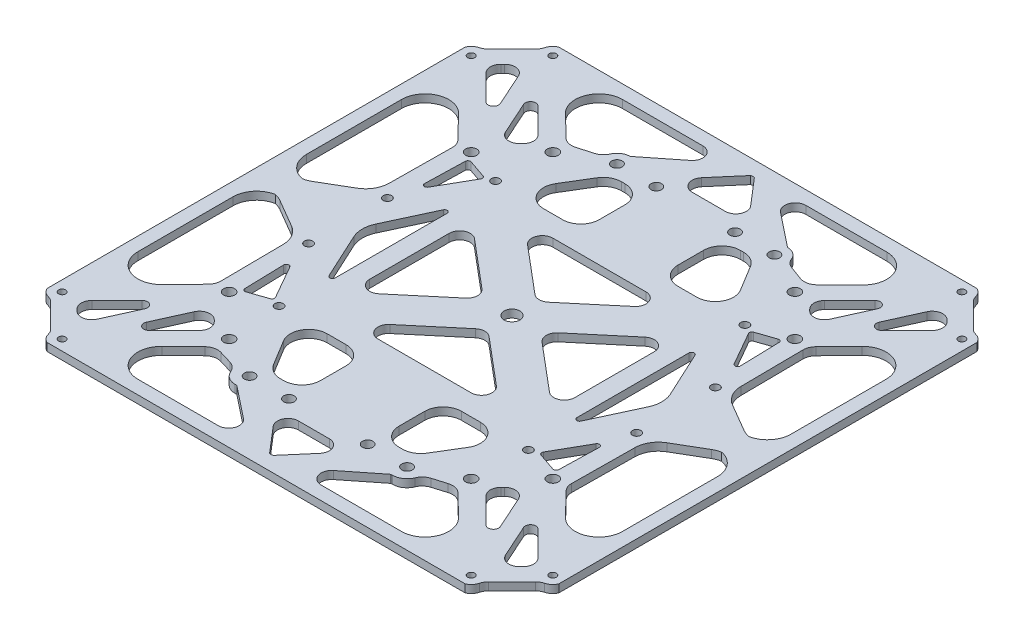
SolidWorks part; units mm, degrees
material "Thornel Mat VMA"
ref_plane "Front Plane" through (0, 0, 0) normal (0, 0, 1) x (1, 0, 0)
ref_plane "Top Plane" through (0, 0, 0) normal (0, 1, 0) x (1, 0, 0)
ref_plane "Right Plane" through (0, 0, 0) normal (1, 0, 0) x (0, 0, -1)
sketch "Sketch2" plane through (0, 0, 0) normal (0, 1, 0) x (1, 0, 0)
  line L1 (-97.5, -97.5) -> (97.5, -97.5)
  line L2 (-97.5, -97.5) -> (-97.5, 97.5)
  line L3 (-97.5, 97.5) -> (97.5, 97.5)
  line L4 (97.5, -97.5) -> (97.5, 97.5)
  line L5 (-97.5, -97.5) -> (97.5, 97.5) construction
  line L6 (-97.5, 97.5) -> (97.5, -97.5) construction
  point P0 (0, 0)
  dimension "D1" = 195
  dimension "D2" = 195
extrude "Boss-Extrude1" add sketch "Sketch2" along normal blind 3
sketch "Sketch3" plane through (0, 3, 0) normal (0, 1, 0) x (1, 0, 0)
  circle A2 centre (47.5, 41.25) radius 1.6
  circle A3 centre (47.5, -41.25) radius 1.6
  circle A4 centre (-47.5, -41.25) radius 1.6
  circle A5 centre (-47.5, 41.25) radius 1.6
  dimension "D3" = 3.2
extrude "Cut-Extrude1" cut sketch "Sketch3" against normal through all both and the other way through all
sketch "Sketch4" plane through (0, 3, 0) normal (0, 1, 0) x (1, 0, 0)
  line L4 (97.5, 97.5) -> (-97.5, 97.5) construction
  circle A0 centre (46.1238, 61.6802) radius 2.11
  circle A3 centre (-61.6802, 46.1238) radius 2.11
  circle A5 centre (-77.9437, 93.5) radius 1.35
  circle A6 centre (-93.5, 77.9437) radius 1.35
  circle A7 centre (-46.1238, 61.6802) radius 2.11
  circle A8 centre (93.5, 77.9437) radius 1.35
  circle A9 centre (77.9437, 93.5) radius 1.35
  circle A10 centre (61.6802, 46.1238) radius 2.11
  circle A11 centre (61.6802, -46.1238) radius 2.11
  circle A12 centre (77.9437, -93.5) radius 1.35
  circle A13 centre (93.5, -77.9437) radius 1.35
  circle A14 centre (-46.1238, -61.6802) radius 2.11
  circle A15 centre (-93.5, -77.9437) radius 1.35
  circle A16 centre (-77.9437, -93.5) radius 1.35
  circle A17 centre (-61.6802, -46.1238) radius 2.11
  circle A18 centre (46.1238, -61.6802) radius 2.11
  dimension "D1" = 2.7
  dimension "D3" = 4.22
  dimension "D6" = 4
extrude "Cut-Extrude2" cut sketch "Sketch4" against normal through all both and the other way through all
sketch "Sketch5" plane through (0, 3, 0) normal (0, 1, 0) x (1, 0, 0)
  circle A1 centre (30, 70) radius 2
  circle A2 centre (15, 70) radius 2
  circle A3 centre (-15, 70) radius 2
  circle A4 centre (-30, 70) radius 2
  circle A5 centre (-30, -70) radius 2
  circle A6 centre (-15, -70) radius 2
  circle A7 centre (15, -70) radius 2
  circle A8 centre (30, -70) radius 2
  dimension "D3" = 4
  dimension "D4" = 4
  dimension "D1" = 4
  dimension "D2" = 4
  dimension "D5" = 4
  dimension "D6" = 4
  dimension "D7" = 4
  dimension "D8" = 4
extrude "Cut-Extrude3" cut sketch "Sketch5" against normal through all both and the other way through all
sketch "Sketch6" plane through (0, 3, 0) normal (0, 1, 0) x (1, 0, 0)
  circle A2 centre (-62.5, 15) radius 1.6
  circle A3 centre (-62.5, -15) radius 1.6
  circle A4 centre (62.5, -15) radius 1.6
  circle A5 centre (62.5, 15) radius 1.6
  dimension "D2" = 3.2
extrude "Cut-Extrude4" cut sketch "Sketch6" against normal through all both and the other way through all
sketch "Sketch7" plane through (0, 3, 0) normal (0, 1, 0) x (1, 0, 0)
  line L0 (-68.2257, 47.6002) -> (-92.338, 72.3986)
  line L1 (-92.3432, 83.4505) -> (-83.4505, 92.3432)
  line L2 (-72.3986, 92.338) -> (-48.2358, 68.8437)
  line L3 (-43.3841, 67.6187) -> (-37.7917, 69.2071)
  line L4 (-67.1, 15) -> (-66.8107, 44.0648)
  line L5 (-30, 75) -> (-15, 75)
  line L6 (-15, 75) -> (15, 75)
  line L7 (15, 75) -> (30, 75)
  line L8 (37.5401, 69.065) -> (42.7993, 67.1289)
  line L9 (48.04, 68.2636) -> (72.4199, 92.3408)
  line L10 (83.4505, 92.3432) -> (92.3432, 83.4505)
  line L11 (68.2257, 47.6002) -> (92.338, 72.3986)
  line L12 (66.8107, 44.0648) -> (67.1, 15)
  line L13 (-67.1, -15) -> (-67.0991, 15.0916)
  line L14 (66.8107, -44.0648) -> (67.1, -15)
  line L15 (68.2257, -47.6002) -> (92.338, -72.3986)
  line L16 (83.4505, -92.3432) -> (92.3432, -83.4505)
  line L17 (48.2358, -68.8437) -> (72.3986, -92.338)
  line L18 (38.2846, -69.1587) -> (43.3041, -67.6421)
  line L19 (15, -75.5) -> (30, -75.5)
  line L20 (-15, -75.5) -> (15, -75.5)
  line L21 (-30, -75.5) -> (-15, -75.5)
  line L22 (-67.1, -15) -> (-66.8107, -44.0648)
  line L23 (-43.3041, -67.6421) -> (-38.2846, -69.1587)
  line L24 (-72.3986, -92.338) -> (-48.2358, -68.8437)
  line L25 (-92.3432, -83.4505) -> (-83.4505, -92.3432)
  line L26 (-68.2257, -47.6002) -> (-92.338, -72.3986)
  line L27 (67.0991, -15.0916) -> (67.1, 15)
  line L29 (-123.1678, -119.5363) -> (123.1678, -119.5363)
  line L30 (-123.1678, -119.5363) -> (-123.1678, 119.5363)
  line L31 (-123.1678, 119.5363) -> (123.1678, 119.5363)
  line L32 (123.1678, -119.5363) -> (123.1678, 119.5363)
  line L33 (-123.1678, -119.5363) -> (123.1678, 119.5363) construction
  line L34 (-123.1678, 119.5363) -> (123.1678, -119.5363) construction
  arc A0 (68.2257, 47.6002) -> (66.8107, 44.0648) centre (71.8104, 44.1146) ccw
  arc A1 (42.7993, 67.1289) -> (48.04, 68.2636) centre (44.5266, 71.8211) ccw
  arc A2 (37.5401, 69.065) -> (34.6337, 71.8786) centre (39.2674, 73.7571) cw
  arc A3 (-37.7917, 69.2071) -> (-34.5789, 72.0084) centre (-39.1578, 74.0168) ccw
  arc A4 (-48.2358, 68.8437) -> (-43.3841, 67.6187) centre (-44.7502, 72.4285) ccw
  arc A5 (-66.8107, 44.0648) -> (-68.2257, 47.6002) centre (-71.8104, 44.1146) ccw
  arc A6 (-92.338, 72.3986) -> (-94.6272, 73.7422) centre (-95.9228, 68.913) ccw
  arc A7 (-72.3986, 92.338) -> (-73.7422, 94.6272) centre (-68.913, 95.9228) cw
  arc A8 (-82.1505, 94.6067) -> (-83.4505, 92.3432) centre (-86.986, 95.8787) cw
  arc A9 (-92.3432, 83.4505) -> (-94.6067, 82.1505) centre (-95.8787, 86.986) cw
  arc A10 (92.338, 72.3986) -> (94.6272, 73.7422) centre (95.9228, 68.913) cw
  circle A11 centre (-93.5, 77.9437) radius 4.35
  arc A12 (-94.6067, 82.1505) -> (-94.6272, 73.7422) centre (-93.5, 77.9437) ccw
  arc A13 (92.3432, 83.4505) -> (94.6067, 82.1505) centre (95.8787, 86.986) ccw
  arc A14 (83.4505, 92.3432) -> (82.1505, 94.6067) centre (86.986, 95.8787) cw
  arc A15 (72.4199, 92.3408) -> (73.7392, 94.6158) centre (68.9065, 95.8983) ccw
  arc A16 (67.1, -15) -> (67.0991, -15.0916) centre (62.5, -15) cw
  arc A17 (-67.0991, -15.0916) -> (-67.1, -15) centre (-62.5, -15) cw
  arc A18 (94.6272, -73.7422) -> (94.6067, -82.1505) centre (93.5, -77.9437) cw
  arc A19 (82.1505, -94.6067) -> (73.7422, -94.6272) centre (77.9437, -93.5) cw
  arc A20 (35.097, -72.0664) -> (30, -75.5) centre (30, -70) cw
  circle A21 centre (-77.9437, 93.5) radius 4.35
  arc A22 (-73.7422, 94.6272) -> (-82.1505, 94.6067) centre (-77.9437, 93.5) ccw
  arc A23 (-30, -75.5) -> (-35.097, -72.0664) centre (-30, -70) cw
  arc A24 (-73.7422, -94.6272) -> (-82.1505, -94.6067) centre (-77.9437, -93.5) cw
  arc A25 (72.3986, -92.338) -> (73.7422, -94.6272) centre (68.913, -95.9228) cw
  arc A26 (83.4505, -92.3432) -> (82.1505, -94.6067) centre (86.986, -95.8787) ccw
  arc A27 (92.3432, -83.4505) -> (94.6067, -82.1505) centre (95.8787, -86.986) cw
  arc A28 (-94.6067, -82.1505) -> (-94.6272, -73.7422) centre (-93.5, -77.9437) cw
  arc A29 (92.338, -72.3986) -> (94.6272, -73.7422) centre (95.9228, -68.913) ccw
  arc A30 (-92.3432, -83.4505) -> (-94.6067, -82.1505) centre (-95.8787, -86.986) ccw
  arc A31 (-82.1505, -94.6067) -> (-83.4505, -92.3432) centre (-86.986, -95.8787) ccw
  arc A32 (-72.3986, -92.338) -> (-73.7422, -94.6272) centre (-68.913, -95.9228) ccw
  arc A33 (-92.338, -72.3986) -> (-94.6272, -73.7422) centre (-95.9228, -68.913) cw
  arc A34 (-66.8107, -44.0648) -> (-68.2257, -47.6002) centre (-71.8104, -44.1146) cw
  arc A36 (-48.2358, -68.8437) -> (-43.3041, -67.6421) centre (-44.7502, -72.4285) cw
  arc A38 (-38.2846, -69.1587) -> (-35.097, -72.0664) centre (-39.7307, -73.945) cw
  arc A39 (38.2846, -69.1587) -> (35.097, -72.0664) centre (39.7307, -73.945) ccw
  arc A43 (43.3041, -67.6421) -> (48.2358, -68.8437) centre (44.7502, -72.4285) cw
  arc A44 (68.2257, -47.6002) -> (66.8107, -44.0648) centre (71.8104, -44.1146) cw
  circle A56 centre (-30, 70) radius 5
  arc A57 (-30, 75) -> (-34.5789, 72.0084) centre (-30, 70) ccw
  circle A65 centre (30, 70) radius 5
  arc A66 (34.6337, 71.8786) -> (30, 75) centre (30, 70) ccw
  circle A74 centre (77.9437, 93.5) radius 4.35
  arc A75 (82.1505, 94.6067) -> (73.7392, 94.6158) centre (77.9437, 93.5) ccw
  circle A77 centre (93.5, 77.9437) radius 4.35
  arc A78 (94.6272, 73.7422) -> (94.6067, 82.1505) centre (93.5, 77.9437) ccw
  circle A85 centre (-62.5, 15) radius 4.6
  arc A86 (-67.0991, 15.0916) -> (-67.1, 15) centre (-62.5, 15) ccw
  circle A88 centre (62.5, 15) radius 4.6
  arc A89 (67.1, 15) -> (67.0991, 15.0916) centre (62.5, 15) ccw
  point P16 (35, 70)
  point P24 (-35, 70)
  point P39 (-93.5, 73.5937)
  point P42 (-73.5937, 93.5)
  point P53 (-82.2937, 93.5)
  point P58 (-93.5, 82.2937)
  point P61 (93.5, 73.5937)
  point P69 (93.5, 82.2937)
  point P72 (82.2937, 93.5)
  point P75 (73.5937, 93.5)
  point P76 (0, 0)
  line M55 (97.5, -97.5) -> (97.5, 97.5)
  line M56 (97.5, 97.5) -> (-97.5, 97.5)
  line M57 (-97.5, 97.5) -> (-97.5, -97.5)
  line M58 (-97.5, -97.5) -> (97.5, -97.5)
  dimension "D3" = 5
  dimension "D4" = 5
  dimension "D1" = 3
  dimension "D2" = 3
  dimension "D5" = 3
  dimension "D6" = 3
  dimension "D8" = 3
  dimension "D11" = 3
  dimension "D14" = 3
  dimension "D15" = 3
extrude "Cut-Extrude5" cut sketch "Sketch7" against normal through all both and the other way through all contours A86 L4 A5 L0 A6 A12 A28 A33 L26 A34 L22 A17 L13 M57 | A24 A31 L25 A30 A28 M57 M58 | L29 L32 L31 L30 A78 A18 A19 A24 A28 A12 A22 A75 M55 M58 M57 M56 | A43 L18 A39 A20 L19 L20 L21 A23 A38 L23 A36 L24 A32 A24 A19 A25 L17 M58 | A89 L27 L14 A16 A44 L15 A29 A18 A78 A10 L11 A0 L12 M55 | A27 L16 A26 A19 A18 M58 M55 | A75 A22 A7 L2 A4 L3 A3 A57 L5 L6 L7 A66 A2 L8 A1 L9 A15 M56 | A22 A12 A9 L1 A8 M56 M57 | A78 A75 A14 L10 A13 M55 M56 region at (-83.5018, 3, 0) region at (-91.2706, 3, -91.2706) region at (-91.2706, 3, 91.2706) region at (0.1643, 3, -85.7939) region at (0, 3, 85.9801) region at (91.2706, 3, -91.2706) region at (91.2706, 3, 91.2706) region at (83.5018, 3, 0) region at (-119.7351, 3, 0) body kept at (-79.6532, 0, 97.5)
sketch "Sketch8" plane through (0, 3, 0) normal (0, 1, 0) x (1, 0, 0)
  line L14 (-46.0759, -21.349) -> (-46.0759, 21.3635)
  line L23 (56.1243, 4.2494) -> (47.983, 21.7846)
  line L24 (-47.9835, -21.7689) -> (-56.1299, -4.1605)
  line L25 (-56.1243, 4.2494) -> (-47.983, 21.7846)
  line L26 (47.9835, -21.7689) -> (56.1299, -4.1605)
  line L27 (46.0759, -21.349) -> (46.0759, 21.3635)
  line L30 (-58.3187, 26.3483) -> (-51.0349, 39.095)
  line L31 (-51.5781, 40.5368) -> (-58.4638, 42.9035)
  line L32 (-59.7885, 41.9842) -> (-60.1866, 26.8708)
  line L33 (-59.7885, -41.9842) -> (-60.1866, -26.8708)
  line L35 (59.7885, 41.9842) -> (60.1866, 26.8708)
  line L36 (51.5781, 40.5368) -> (58.4638, 42.9035)
  line L37 (58.3187, 26.3483) -> (51.0349, 39.095)
  line L38 (-51.5781, -40.5368) -> (-58.4638, -42.9035)
  line L39 (-58.3187, -26.3483) -> (-51.0349, -39.095)
  line L40 (58.3187, -26.3483) -> (51.0349, -39.095)
  line L41 (51.5781, -40.5368) -> (58.4638, -42.9035)
  line L42 (59.7885, -41.9842) -> (60.1866, -26.8708)
  line L43 (-29.1909, -41.25) -> (-22, -41.25)
  line L44 (-15, -48.25) -> (-15, -58)
  line L46 (-22, -65) -> (-23.2561, -65)
  line L47 (-29.2355, -61.6396) -> (-35.1703, -51.8896)
  line L48 (29.1909, 41.25) -> (22, 41.25)
  line L50 (29.2355, -61.6396) -> (35.1703, -51.8896)
  line L51 (22, -65) -> (23.2561, -65)
  line L52 (15, -48.25) -> (15, -58)
  line L53 (29.1909, -41.25) -> (22, -41.25)
  line L54 (15, 48.25) -> (15, 58)
  line L55 (22, 65) -> (23.2561, 65)
  line L56 (29.2355, 61.6396) -> (35.1703, 51.8896)
  line L57 (-29.2355, 61.6396) -> (-35.1703, 51.8896)
  line L58 (-22, 65) -> (-23.2561, 65)
  line L59 (-15, 48.25) -> (-15, 58)
  line L60 (-29.1909, 41.25) -> (-22, 41.25)
  line L64 (-55.3178, 58.1431) -> (-54.6091, 58.8518)
  line L65 (-54.6091, 64.5086) -> (-64.2157, 74.1152)
  line L66 (-84.3061, 81.4807) -> (-85.0147, 80.7721)
  line L67 (-85.0147, 75.1152) -> (-75.4082, 65.5087)
  line L68 (55.3178, -58.1431) -> (54.6091, -58.8518)
  line L69 (-77.8313, 80.2967) -> (-72.1708, 67.7451)
  line L70 (-67.453, 71.8787) -> (-61.7925, 59.3271)
  line L71 (-32.5, -18.2077) -> (-14.5052, -3.0601)
  line L72 (67.453, 71.8787) -> (61.7925, 59.3271)
  line L73 (77.8313, 80.2967) -> (72.1708, 67.7451)
  line L74 (85.0147, 75.1152) -> (75.4082, 65.5087)
  line L75 (84.3061, 81.4807) -> (85.0147, 80.7721)
  line L76 (54.6091, 64.5086) -> (64.2157, 74.1152)
  line L77 (55.3178, 58.1431) -> (54.6091, 58.8518)
  line L78 (54.6091, -64.5086) -> (64.2157, -74.1152)
  line L79 (84.3061, -81.4807) -> (85.0147, -80.7721)
  line L80 (85.0147, -75.1152) -> (75.4082, -65.5087)
  line L81 (77.8313, -80.2967) -> (72.1708, -67.7451)
  line L82 (67.453, -71.8787) -> (61.7925, -59.3271)
  line L83 (-67.453, -71.8787) -> (-61.7925, -59.3271)
  line L84 (-77.8313, -80.2967) -> (-72.1708, -67.7451)
  line L85 (-85.0147, -75.1152) -> (-75.4082, -65.5087)
  line L86 (-84.3061, -81.4807) -> (-85.0147, -80.7721)
  line L87 (-54.6091, -64.5086) -> (-64.2157, -74.1152)
  line L88 (-55.3178, -58.1431) -> (-54.6091, -58.8518)
  line L89 (-32.5, 18.2077) -> (-14.5052, 3.0601)
  line L90 (-39.0759, -15.1476) -> (-39.0759, 15.1476)
  line L91 (-20.3144, 26.25) -> (-2.5759, 11.3182)
  line L92 (2.5759, 11.3182) -> (20.3144, 26.25)
  line L93 (-17.7385, 33.3101) -> (17.7385, 33.3101)
  line L94 (32.5, -18.2077) -> (14.5052, -3.0601)
  line L95 (39.0759, 15.1476) -> (39.0759, -15.1476)
  line L96 (14.5052, 3.0601) -> (32.5, 18.2077)
  line L97 (17.7385, -33.3101) -> (-17.7385, -33.3101)
  line L98 (-20.3144, -26.25) -> (-2.5759, -11.3182)
  line L99 (20.3144, -26.25) -> (2.5759, -11.3182)
  circle A13 centre (0, 0) radius 3
  arc A14 (-46.0759, -21.349) -> (-47.9835, -21.7689) centre (-47.0759, -21.349) cw
  arc A15 (-46.0759, 21.3635) -> (-47.983, 21.7846) centre (-47.0759, 21.3635) ccw
  arc A16 (-56.1299, -4.1605) -> (-56.1243, 4.2494) centre (-47.0542, 0.0383) cw
  arc A17 (56.1299, -4.1605) -> (56.1243, 4.2494) centre (47.0542, 0.0383) ccw
  arc A18 (46.0759, 21.3635) -> (47.983, 21.7846) centre (47.0759, 21.3635) cw
  arc A19 (46.0759, -21.349) -> (47.9835, -21.7689) centre (47.0759, -21.349) ccw
  arc A20 (-58.3187, 26.3483) -> (-60.1866, 26.8708) centre (-59.187, 26.8445) cw
  arc A21 (-51.0349, 39.095) -> (-51.5781, 40.5368) centre (-51.9032, 39.5911) ccw
  arc A22 (-58.4638, 42.9035) -> (-59.7885, 41.9842) centre (-58.7889, 41.9578) ccw
  arc A23 (58.4638, 42.9035) -> (59.7885, 41.9842) centre (58.7889, 41.9578) cw
  arc A24 (51.0349, 39.095) -> (51.5781, 40.5368) centre (51.9032, 39.5911) cw
  arc A25 (58.3187, 26.3483) -> (60.1866, 26.8708) centre (59.187, 26.8445) ccw
  arc A26 (-58.4638, -42.9035) -> (-59.7885, -41.9842) centre (-58.7889, -41.9578) cw
  arc A27 (-51.0349, -39.095) -> (-51.5781, -40.5368) centre (-51.9032, -39.5911) cw
  arc A28 (-58.3187, -26.3483) -> (-60.1866, -26.8708) centre (-59.187, -26.8445) ccw
  arc A29 (58.3187, -26.3483) -> (60.1866, -26.8708) centre (59.187, -26.8445) cw
  arc A30 (51.0349, -39.095) -> (51.5781, -40.5368) centre (51.9032, -39.5911) ccw
  arc A31 (58.4638, -42.9035) -> (59.7885, -41.9842) centre (58.7889, -41.9578) ccw
  arc A32 (-15, -48.25) -> (-22, -41.25) centre (-22, -48.25) ccw
  arc A33 (-29.1909, -41.25) -> (-35.1703, -51.8896) centre (-29.1909, -48.25) ccw
  arc A34 (-29.2355, -61.6396) -> (-23.2561, -65) centre (-23.2561, -58) ccw
  arc A35 (-15, -58) -> (-22, -65) centre (-22, -58) cw
  arc A36 (15, -58) -> (22, -65) centre (22, -58) ccw
  arc A37 (29.2355, -61.6396) -> (23.2561, -65) centre (23.2561, -58) cw
  arc A38 (29.1909, -41.25) -> (35.1703, -51.8896) centre (29.1909, -48.25) cw
  arc A39 (15, -48.25) -> (22, -41.25) centre (22, -48.25) cw
  arc A40 (15, 48.25) -> (22, 41.25) centre (22, 48.25) ccw
  arc A41 (29.1909, 41.25) -> (35.1703, 51.8896) centre (29.1909, 48.25) ccw
  arc A42 (29.2355, 61.6396) -> (23.2561, 65) centre (23.2561, 58) ccw
  arc A43 (15, 58) -> (22, 65) centre (22, 58) cw
  arc A44 (-15, 58) -> (-22, 65) centre (-22, 58) ccw
  arc A45 (-29.2355, 61.6396) -> (-23.2561, 65) centre (-23.2561, 58) cw
  arc A46 (-29.1909, 41.25) -> (-35.1703, 51.8896) centre (-29.1909, 48.25) cw
  arc A47 (-15, 48.25) -> (-22, 41.25) centre (-22, 48.25) cw
  arc A48 (-55.3178, 58.1431) -> (-61.7925, 59.3271) centre (-58.1462, 60.9716) cw
  arc A49 (-54.6091, 58.8518) -> (-54.6091, 64.5086) centre (-57.4376, 61.6802) ccw
  arc A50 (-77.8313, 80.2967) -> (-84.3061, 81.4807) centre (-81.4777, 78.6523) ccw
  arc A51 (-85.0147, 80.7721) -> (-85.0147, 75.1152) centre (-82.1863, 77.9437) ccw
  arc A52 (-64.2157, 74.1152) -> (-67.453, 71.8787) centre (-65.6299, 72.7009) ccw
  arc A53 (-72.1708, 67.7451) -> (-75.4082, 65.5087) centre (-73.994, 66.9229) cw
  arc A54 (72.1708, 67.7451) -> (75.4082, 65.5087) centre (73.994, 66.9229) ccw
  arc A55 (64.2157, 74.1152) -> (67.453, 71.8787) centre (65.6299, 72.7009) cw
  arc A56 (85.0147, 80.7721) -> (85.0147, 75.1152) centre (82.1863, 77.9437) cw
  arc A57 (77.8313, 80.2967) -> (84.3061, 81.4807) centre (81.4777, 78.6523) cw
  arc A58 (54.6091, 58.8518) -> (54.6091, 64.5086) centre (57.4376, 61.6802) cw
  arc A59 (55.3178, 58.1431) -> (61.7925, 59.3271) centre (58.1462, 60.9716) ccw
  arc A60 (55.3178, -58.1431) -> (61.7925, -59.3271) centre (58.1462, -60.9716) cw
  arc A61 (54.6091, -58.8518) -> (54.6091, -64.5086) centre (57.4376, -61.6802) ccw
  arc A62 (77.8313, -80.2967) -> (84.3061, -81.4807) centre (81.4777, -78.6523) ccw
  arc A63 (85.0147, -80.7721) -> (85.0147, -75.1152) centre (82.1863, -77.9437) ccw
  arc A64 (64.2157, -74.1152) -> (67.453, -71.8787) centre (65.6299, -72.7009) ccw
  arc A65 (72.1708, -67.7451) -> (75.4082, -65.5087) centre (73.994, -66.9229) cw
  arc A66 (-72.1708, -67.7451) -> (-75.4082, -65.5087) centre (-73.994, -66.9229) ccw
  arc A67 (-64.2157, -74.1152) -> (-67.453, -71.8787) centre (-65.6299, -72.7009) cw
  arc A68 (-85.0147, -80.7721) -> (-85.0147, -75.1152) centre (-82.1863, -77.9437) cw
  arc A69 (-77.8313, -80.2967) -> (-84.3061, -81.4807) centre (-81.4777, -78.6523) cw
  arc A70 (-54.6091, -58.8518) -> (-54.6091, -64.5086) centre (-57.4376, -61.6802) cw
  arc A71 (-55.3178, -58.1431) -> (-61.7925, -59.3271) centre (-58.1462, -60.9716) ccw
  arc A84 (-20.3144, 26.25) -> (-17.7385, 33.3101) centre (-17.7385, 29.3101) cw
  arc A85 (-2.5759, 11.3182) -> (2.5759, 11.3182) centre (0, 14.3784) ccw
  arc A86 (20.3144, 26.25) -> (17.7385, 33.3101) centre (17.7385, 29.3101) ccw
  arc A87 (39.0759, 15.1476) -> (32.5, 18.2077) centre (35.0759, 15.1476) ccw
  arc A88 (14.5052, -3.0601) -> (14.5052, 3.0601) centre (17.0811, 0) cw
  arc A89 (32.5, -18.2077) -> (39.0759, -15.1476) centre (35.0759, -15.1476) ccw
  arc A90 (17.7385, -33.3101) -> (20.3144, -26.25) centre (17.7385, -29.3101) ccw
  arc A91 (-2.5759, -11.3182) -> (2.5759, -11.3182) centre (0, -14.3784) cw
  arc A92 (-17.7385, -33.3101) -> (-20.3144, -26.25) centre (-17.7385, -29.3101) cw
  arc A93 (-32.5, -18.2077) -> (-39.0759, -15.1476) centre (-35.0759, -15.1476) cw
  arc A94 (-14.5052, -3.0601) -> (-14.5052, 3.0601) centre (-17.0811, 0) ccw
  arc A95 (-32.5, 18.2077) -> (-39.0759, 15.1476) centre (-35.0759, 15.1476) ccw
  point P50 (-58.0759, 0.0458)
  point P61 (58.0759, 0.0458)
  dimension "D1" = 4
  dimension "D4" = 1
  dimension "D5" = 10
  dimension "D6" = 1
  dimension "D7" = 7
  dimension "D8" = 4
  dimension "D9" = 2
  dimension "D3" = 12
extrude "Cut-Extrude7" cut sketch "Sketch8" against normal through all both and the other way through all
sketch "Sketch9" plane through (0, 0, 0) normal (0, 1, 0) x (1, 0, 0)
  line L0 (-76.2341, 97.5) -> (76.2341, 97.5)
  line L1 (-97.5, 76.2341) -> (-92.338, 76.2341)
  line L2 (-97.5, 76.2341) -> (-97.5, -76.2341)
  line L3 (-97.5, -76.2341) -> (-92.338, -76.2341)
  line L4 (-92.338, 76.2341) -> (-92.338, -76.2341)
  line L5 (-72.3986, 92.338) -> (75.7801, 92.338)
  line L6 (92.338, 76.2341) -> (92.338, -76.2341)
  line L7 (97.5, -76.2341) -> (92.338, -76.2341)
  line L8 (97.5, 76.2341) -> (97.5, -76.2341)
  line L9 (97.5, 76.2341) -> (92.338, 76.2341)
  line L11 (75.7801, 92.338) -> (76.2341, 97.5)
  line L12 (-76.2341, 97.5) -> (-74.9539, 93.3918)
  line L13 (-74.9539, 93.3918) -> (-72.3986, 92.338)
  line L15 (-74.9539, -93.3918) -> (-72.3986, -92.338)
  line L16 (-76.2341, -97.5) -> (-74.9539, -93.3918)
  line L17 (75.7801, -93.3918) -> (76.2341, -97.5)
  line L18 (72.3986, -92.338) -> (75.7801, -93.3918)
  line L19 (-72.3986, -92.338) -> (72.3986, -92.338)
  line L20 (-76.2341, -97.5) -> (76.2341, -97.5)
  point P7 (0, 0)
  point P17 (75.7801, 92.338)
  point P18 (75.8172, 92.2986)
extrude "Boss-Extrude2" add sketch "Sketch9" along normal up to surface (3 mm away) up to face at (56.578, 3, 36.2456)
fillet "Fillet1" radius 9 8 edges at (-72.3986, 1.5, 92.338) (-92.338, 1.5, 72.3986) (92.338, 1.5, 72.3986) (72.3986, 1.5, 92.338) (92.338, 1.5, -72.3986) (72.4171, 1.5, -92.338) (-72.3986, 1.5, -92.338) (-92.338, 1.5, -72.3986)
sketch "Sketch10" plane through (0, 0, 0) normal (0, -1, 0) x (1, 0, 0)
  line L0 (0.1317, -92.338) -> (15, -75)
  line L1 (50.4957, -92.338) -> (-50.2322, -92.338) construction
  line L2 (-30, -75) -> (30, -75) construction
  line L3 (15, -75) -> (30, -75)
  line L4 (30, -75) -> (8.1317, -92.338)
  line L5 (8.1317, -92.338) -> (0.1317, -92.338)
  line L7 (-8.1317, -92.338) -> (-0.1317, -92.338)
  line L8 (-30, -75) -> (-8.1317, -92.338)
  line L9 (-15, -75) -> (-30, -75)
  line L10 (-0.1317, -92.338) -> (-15, -75)
  line L11 (-0.1317, 92.338) -> (-15, 75)
  line L12 (-15, 75) -> (-30, 75)
  line L13 (-30, 75) -> (-8.1317, 92.338)
  line L14 (-8.1317, 92.338) -> (-0.1317, 92.338)
  line L15 (8.1317, 92.338) -> (0.1317, 92.338)
  line L16 (30, 75) -> (8.1317, 92.338)
  line L17 (15, 75) -> (30, 75)
  line L18 (0.1317, 92.338) -> (15, 75)
  line L23 (0, 0) -> (0, 24.1776) construction
  line L36 (-92.338, -5) -> (-84.338, -5)
  line L37 (-92.338, 5) -> (-84.338, 5)
  line L38 (-84.338, 5) -> (-67.0991, 15.0916)
  line L39 (-67.0991, 15.0916) -> (-67.0991, -15.0916)
  line L40 (-67.0991, -15.0916) -> (-84.338, -5)
  line L41 (-92.338, 5) -> (-92.338, -5)
  line L42 (92.338, 5) -> (92.338, -5)
  line L43 (67.0991, -15.0916) -> (84.338, -5)
  line L44 (67.0991, 15.0916) -> (67.0991, -15.0916)
  line L45 (84.338, 5) -> (67.0991, 15.0916)
  line L46 (92.338, 5) -> (84.338, 5)
  line L47 (92.338, -5) -> (84.338, -5)
  dimension "D1" = 8
extrude "Boss-Extrude3" add sketch "Sketch10" against normal up to surface (3 mm away) contours L7 L10 L9 L8 | L5 L4 L3 L0 | L39 | L15 L18 L17 L16 | L14 L13 L12 L11 | L41 L36 L40 L39 L38 L37 | L42 L47 L43 L44 L45 L46 region at (14.2476, 0, -82.7895) region at (-14.2476, 0, -82.7895) region at (-14.2476, 0, 82.7895) region at (14.2476, 0, 82.7895) up to face at (0, 3, 74.8987)
fillet "Fillet2" radius 9 12 edges at (84.338, 1.5, 5) (92.338, 1.5, 5) (67.0991, 1.5, 15.0916) (84.338, 1.5, -5) (92.338, 1.5, -5) (67.0991, 1.5, -15.0916) (-84.338, 1.5, 5) (-92.338, 1.5, 5) (-84.338, 1.5, -5) (-92.338, 1.5, -5) (-67.0991, 1.5, -15.0916) (-67.0991, 1.5, 15.0916)
fillet "Fillet3" radius 4 8 edges at (14.5712, 1.5, 75.5) (-14.5712, 1.5, 75.5) (-8.1317, 1.5, 92.338) (8.1317, 1.5, 92.338) (-15, 1.5, -75) (15, 1.5, -75) (8.1317, 1.5, -92.338) (-8.1317, 1.5, -92.338)
sketch "Sketch11" plane through (0, 0, 0) normal (0, -1, 0) x (1, 0, 0)
  line L0 (-1.5025, 92.338) -> (1.4975, 92.338)
  line L1 (-1.5025, 91.838) -> (-1.5025, 90.838) construction
  line L2 (0, 0) -> (117.3836, 0) construction
  line L3 (1.4975, 91.838) -> (1.4975, 90.838) construction
  line L4 (-2.0025, 92.338) -> (1.9975, 92.338) construction
  line L5 (-1.5025, -92.338) -> (-1.5025, -90.838)
  line L6 (1.4975, 92.338) -> (1.4975, 90.838)
  line L7 (1.4975, -92.338) -> (1.4975, -90.838)
  line L8 (-1.5025, 92.338) -> (-1.5025, 90.838)
  line L9 (-1.5025, 91.838) -> (1.4975, 91.838) construction
  line L10 (-2.0025, 92.338) -> (-2.0025, 90.838) construction
  line L11 (-1.5025, -92.338) -> (1.4975, -92.338)
  line L14 (1.9975, 92.338) -> (1.9975, 90.838) construction
  arc A0 (-1.5025, 90.838) -> (1.4975, 90.838) centre (-0.0025, 90.1655) cw
  arc A1 (-1.5025, -90.838) -> (1.4975, -90.838) centre (-0.0025, -90.1655) ccw
  point P3 (-0.0025, 92.338)
  point P19 (-0.0025, -92.338)
  dimension "D4" = 0.5
extrude "Boss-Extrude4" add sketch "Sketch11" against normal up to surface (3 mm away) up to face at (78.3031, 3, -28.8709)
